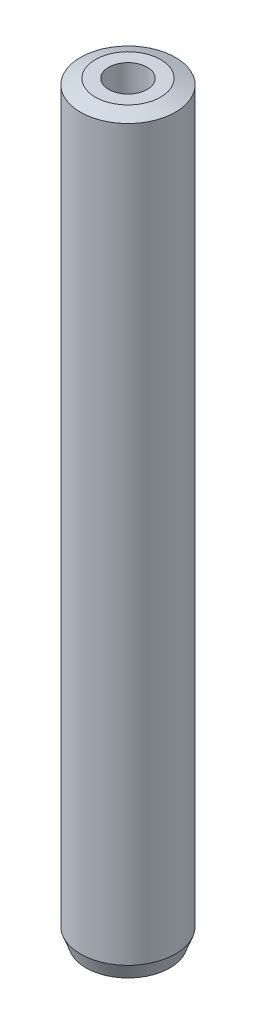
SolidWorks part; units mm, degrees
ref_plane "Front Plane" through (0, 0, 0) normal (0, 0, 1) x (1, 0, 0)
ref_plane "Top Plane" through (0, 0, 0) normal (0, 1, 0) x (1, 0, 0)
ref_plane "Right Plane" through (0, 0, 0) normal (1, 0, 0) x (0, 0, -1)
sketch "Sketch1" plane through (0, 0, 0) normal (0, 1, 0) x (1, 0, 0)
  circle A0 centre (0, 0) radius 12.5
  dimension "SHAFT_OD" = 25
extrude "Boss-Extrude1" add sketch "Sketch1" along normal blind 197.2373
sketch "Sketch2" plane through (0, 0, 0) normal (0, 1, 0) x (1, 0, 0)
  circle A0 centre (0, 0) radius 5.069
  dimension "BORE_D" = 10.138
extrude "Cut-Extrude1" cut sketch "Sketch2" along normal through all
chamfer "Chamfer1" distance 1.4673 angle 69.49 2 edges at (0, 197.2373, 12.5) (0, 0, 12.5) first distance on face at (0, 197.2373, 12.5) first distance on face at (0, 0, 5.069)
